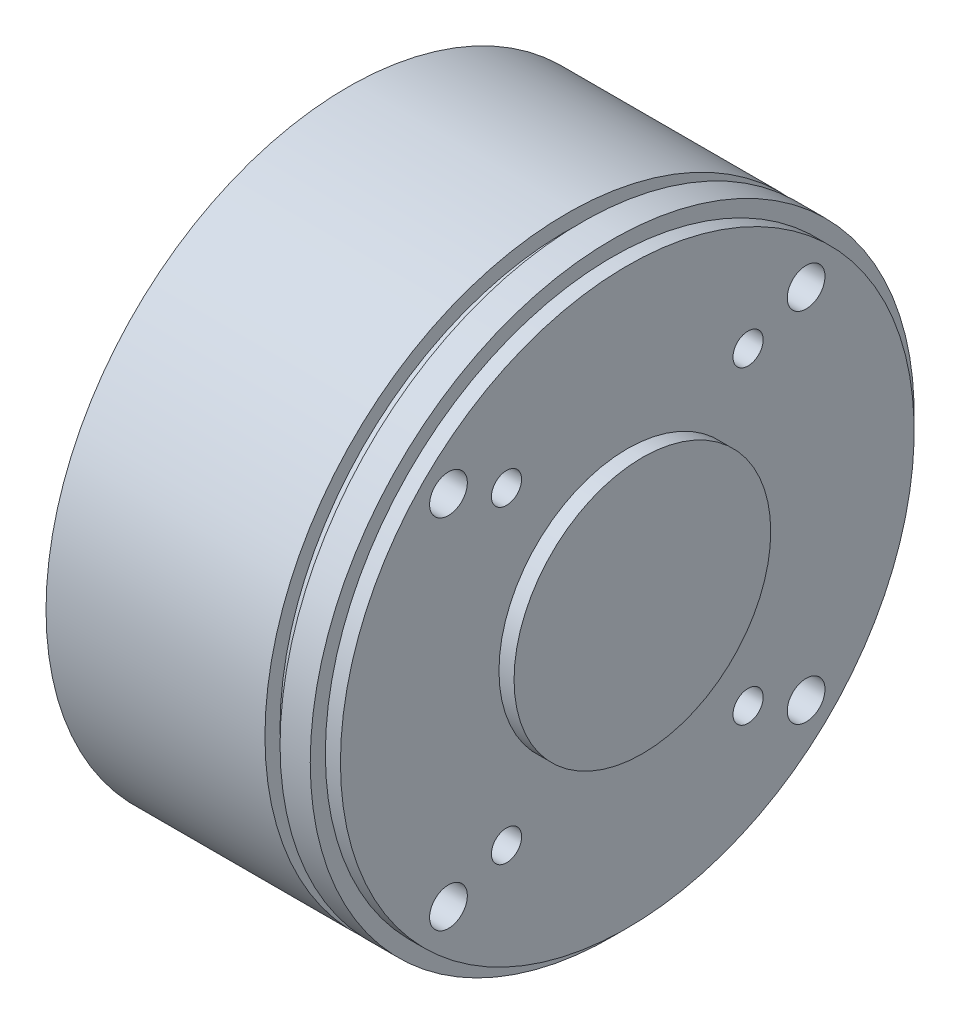
SolidWorks part; units mm, degrees
ref_plane "前视基准面" through (0, 0, 0) normal (0, 0, 1) x (1, 0, 0)
ref_plane "上视基准面" through (0, 0, 0) normal (0, 1, 0) x (1, 0, 0)
ref_plane "右视基准面" through (0, 0, 0) normal (1, 0, 0) x (0, 0, -1)
other "Configuration Table"
sketch "草图1" plane through (0, 0, 0) normal (0, 1, 0) x (1, 0, 0)
  line L0 (-9.6464, 0) -> (8.899, 0) construction
  line L1 (0, 0) -> (0, 19) construction
  line L2 (0, 19) -> (1, 19)
  line L3 (1, 19) -> (1, 20)
  line L4 (1, 20) -> (3, 20)
  line L5 (3, 20) -> (3, 19)
  line L6 (3, 19) -> (4, 19)
  line L7 (4, 19) -> (4, 8.5)
  line L8 (4, 8.5) -> (5, 8.5)
  line L9 (5, 8.5) -> (5, 0)
  line L10 (0, 0) -> (5, 0)
  line L11 (0, 19) -> (0, 20)
  line L12 (0, 20) -> (-14.5, 20)
  line L13 (-14.5, 20) -> (-14.5, 15)
  line L14 (-14.5, 15) -> (-15, 15)
  line L15 (-15, 15) -> (-15, 0)
  line L16 (-15, 0) -> (0, 0)
  dimension "D1" = 1
  dimension "D2" = 1
  dimension "D3" = 2
  dimension "D4" = 1
  dimension "D5" = 20
  dimension "D6" = 19
  dimension "D7" = 8.5
  dimension "D8" = 15
  dimension "D9" = 20
  dimension "D10" = 0.5
revolve "旋转1" add sketch "草图1" angle 360 about L0
chamfer "倒角1" distance 0.5 angle 45 1 edges at (-14.5, 0, 15)
sketch "草图2" plane through (-15, 0, 0) normal (-1, 0, 0) x (0, 0, 1)
  line L0 (-21.98, 0) -> (22.6908, 0) construction
  line L1 (0, 22.7485) -> (0, -21.9381) construction
  circle A0 centre (0, 10) radius 1.5
  circle A1 centre (10, 0) radius 1.5
  circle A2 centre (0, -10) radius 1.5
  circle A3 centre (-10, 0) radius 1.5
  point P15 (0, 0)
  dimension "D1" = 3
  dimension "D2" = 10
  dimension "D3" = 4
extrude "切除-拉伸1" cut sketch "草图2" against normal blind 5
sketch "草图3" plane through (5, 0, 0) normal (1, 0, 0) x (0, 0, -1)
  line L0 (0, 21.5519) -> (0, -21.5179) construction
  line L1 (-25.1751, 0) -> (24.1204, 0) construction
  line L2 (0, 0) -> (-18.5737, 18.5737) construction
  circle A0 centre (-8, 10.25) radius 1
  circle A1 centre (8, 10.25) radius 1
  circle A2 centre (8, -10.25) radius 1
  circle A3 centre (-8, -10.25) radius 1
  circle A4 centre (-11.844, 11.844) radius 1.25
  circle A5 centre (11.844, 11.844) radius 1.25
  circle A6 centre (11.844, -11.844) radius 1.25
  circle A7 centre (-11.844, -11.844) radius 1.25
  point P26 (0, 0)
  dimension "D1" = 2
  dimension "D2" = 16
  dimension "D3" = 20.5
  dimension "D4" = 2.5
  dimension "D6" = 16.75
  dimension "D5" = 45
  dimension "D7" = 4
extrude "切除-拉伸2" cut sketch "草图3" against normal blind 5
